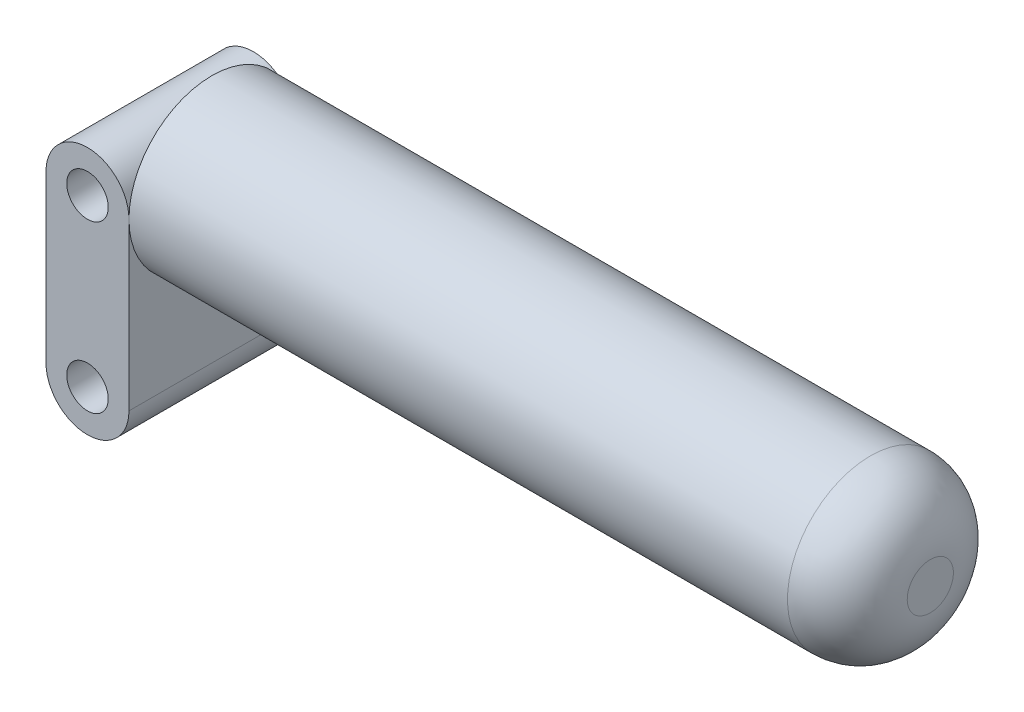
SolidWorks part; units mm, degrees
ref_plane "Plan de face" through (0, 0, 0) normal (0, 0, 1) x (1, 0, 0)
ref_plane "Plan de dessus" through (0, 0, 0) normal (0, 1, 0) x (1, 0, 0)
ref_plane "Plan de droite" through (0, 0, 0) normal (1, 0, 0) x (0, 0, -1)
other "Centre de masse"
sketch "Esquisse1" plane through (0, 0, 0) normal (0, 0, 1) x (1, 0, 0)
  line L0 (0, 10) -> (0, -10) construction
  line L1 (5, 10) -> (5, -10)
  line L2 (-5, 10) -> (-5, -10)
  line L3 (0, 0) -> (16.4339, 0) construction
  arc A0 (5, 10) -> (-5, 10) centre (0, 10) ccw
  arc A1 (-5, -10) -> (5, -10) centre (0, -10) ccw
  circle A2 centre (0, 10) radius 2.5
  circle A3 centre (0, -10) radius 2.5
  point P3 (0, 0)
  dimension "D3" = 5
  dimension "D2" = 10
extrude "Boss.-Extru.1" add sketch "Esquisse1" along normal mid plane 20
sketch "Esquisse2" plane through (5, 0, 0) normal (1, 0, 0) x (0, 0, -1)
  line L0 (0, 11.352) -> (0, 0) construction
  line L1 (0, 0) -> (4.254, 0) construction
  circle A0 centre (0, 10) radius 10
  dimension "D1" = 20
extrude "Boss.-Extru.2" add sketch "Esquisse2" along normal blind 86.6 contours A0
fillet "Congé1" radius 7.2167 1 edges at (91.6, 20, 0)
ref_axis "Axe1" through (0, 10, 10) along (0, 0, -1)
ref_point "Point1"
equation "\"e\"= 0.02m"
equation "\"d\"= 0.05"
equation "\"l\"= 0.01"
equation "\"D2@Esquisse1\"=\"l\""
equation "\"D1@Boss.-Extru.1\"=\"e\""
equation "\"Ddoigt\"= 0.02m"
equation "\"D1@Esquisse2\"=\"Ddoigt\""
equation "\"Ldoigt\"= 0.0866m"
equation "\"D1@Boss.-Extru.2\"=\"Ldoigt\""
equation "\"D1@Congé1\"=\"Ldoigt\"/12m"
